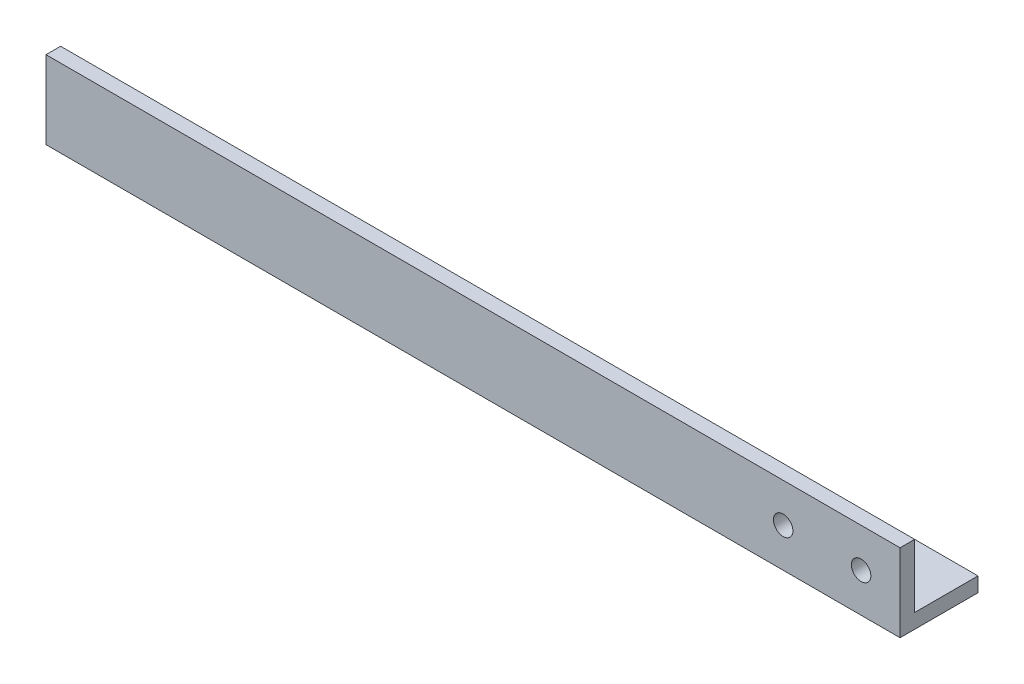
SolidWorks part; units mm, degrees
material "6061 Alloy"
ref_plane "Front Plane" through (0, 0, 0) normal (0, 0, 1) x (1, 0, 0)
ref_plane "Top Plane" through (0, 0, 0) normal (0, 1, 0) x (1, 0, 0)
ref_plane "Right Plane" through (0, 0, 0) normal (1, 0, 0) x (0, 0, -1)
sketch "Sketch1" plane through (0, 0, 0) normal (1, 0, 0) x (0, 0, -1)
  line L0 (0, 0) -> (0, -25.4)
  line L1 (0, -25.4) -> (25.4, -25.4)
  line L2 (25.4, -25.4) -> (25.4, -20.6375)
  line L3 (25.4, -20.6375) -> (4.7625, -20.6375)
  line L4 (4.7625, -20.6375) -> (4.7625, 0)
  line L5 (4.7625, 0) -> (0, 0)
  dimension "D1" = 4.7625
  dimension "D2" = 4.7625
  dimension "D3" = 25.4
  dimension "D4" = 25.4
extrude "Boss-Extrude1" add sketch "Sketch1" along normal blind 278.384
sketch "Sketch2" plane through (0, -20.6375, 0) normal (0, 1, 0) x (1, 0, 0)
  line L1 (0, 25.4) -> (0, 4.7625) construction
  line L2 (278.384, 0) -> (0, 0) construction
  circle A0 centre (9.525, 11.1125) radius 3.175
  circle A1 centre (19.05, 17.4625) radius 3.175
  dimension "D1" = 11.1125
  dimension "D2" = 17.4625
  dimension "D3" = 19.05
  dimension "D4" = 6.35
  dimension "D5" = 6.35
  dimension "D6" = 9.525
extrude "Cut-Extrude1" cut sketch "Sketch2" against normal up to next
sketch "Sketch3" plane through (0, -25.4, 0) normal (0, -1, 0) x (1, 0, 0)
  circle A0 centre (184.0953, -13.4704) radius 3.175 construction
  circle A1 centre (184.0953, -13.4704) radius 3.175
extrude "Cut-Extrude2" cut sketch "Sketch3" against normal up to next
sketch "Sketch6" plane through (0, 0, 0) normal (0, 0, 1) x (1, 0, 0)
  circle A0 centre (240.284, -12.7) radius 3.175 construction
  circle A1 centre (265.684, -12.7) radius 3.175 construction
  circle A2 centre (240.284, -12.7) radius 3.175
  circle A3 centre (265.684, -12.7) radius 3.175
extrude "Cut-Extrude3" cut sketch "Sketch6" against normal up to next
